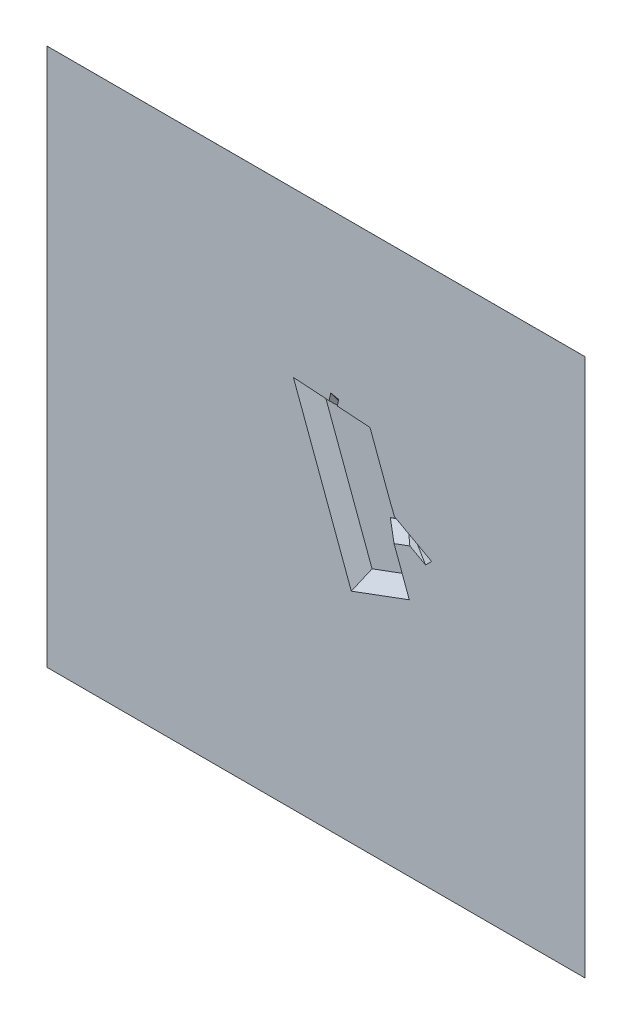
SolidWorks part; units mm, degrees
ref_plane "Front Plane" through (0, 0, 0) normal (0, 0, 1) x (1, 0, 0)
ref_plane "Top Plane" through (0, 0, 0) normal (0, 1, 0) x (1, 0, 0)
ref_plane "Right Plane" through (0, 0, 0) normal (1, 0, 0) x (0, 0, -1)
sketch "Sketch3" plane through (0, 0, 0) normal (0, 0, 1) x (1, 0, 0)
  line L1 (250000, 250000) -> (-250000, 250000)
  line L2 (250000, 250000) -> (250000, -250000)
  line L3 (250000, -250000) -> (-250000, -250000)
  line L4 (-250000, 250000) -> (-250000, -250000)
  line L5 (250000, 250000) -> (-250000, -250000) construction
  line L6 (250000, -250000) -> (-250000, 250000) construction
  point P0 (0, 0)
  dimension "D1" = 500000
  dimension "D2" = 500000
extrude "Boss-Extrude1" add sketch "Sketch3" against normal blind 15000
sketch "Sketch2" plane through (0, 0, 0) normal (0, 0, 1) x (1, 0, 0)
  line L0 (-17377.0412, 88071.2876) -> (32833.2448, -47278.1791)
  line L1 (-17377.0412, 88071.2876) -> (10112.1552, 86264.6887)
  line L2 (10112.1552, 86264.6887) -> (13737.5816, 102715.7946)
  line L3 (13737.5816, 102715.7946) -> (21089.3357, 101095.6455)
  line L4 (21089.3357, 101095.6455) -> (17710.8971, 85765.2969)
  line L5 (68877.8782, 42815.8741) -> (72921.953, 32726.7803)
  line L6 (45501.4717, 34143.9813) -> (68877.8782, 42815.8741) construction
  line L7 (68877.8782, 42815.8741) -> (53825.5063, 83391.8331)
  line L8 (17710.8971, 85765.2969) -> (53825.5063, 83391.8331)
  line L9 (18073.9152, 35635.2282) -> (6825.7271, 65956.4311) construction
  line L10 (32833.2448, -47278.1791) -> (75451.4702, -31468.1923)
  line L11 (75451.4702, -31468.1923) -> (57125.4375, 17932.4176)
  line L12 (57125.4375, 17932.4176) -> (73215.3416, 23901.253)
  line L13 (73215.3416, 23901.253) -> (101844.2457, 8294.7719)
  line L14 (101844.2457, 8294.7719) -> (107465.1822, 13896.2218)
  line L15 (107465.1822, 13896.2218) -> (82661.4814, 27417.4689)
  line L16 (82661.4814, 27417.4689) -> (72921.953, 32726.7803)
  line L17 (66452.5436, 88076.0566) -> (6825.7271, 65956.4311) construction
  line L18 (25140.4514, 16586.3048) -> (19465.1425, 31884.9633) construction
  dimension "D1" = 15000
extrude "Cut-Extrude3" cut sketch "Sketch2" against normal blind 12180
sketch "Sketch4" plane through (19388.8566, -52265.6135, 0) normal (-0.3478, 0.9376, 0) x (0.9376, 0.3478, 0)
  line L0 (14339.6679, 0) -> (26339.6679, 12180)
  line L1 (14339.6679, 12180) -> (59795.8976, 12180) construction
  line L2 (26339.6679, 12180) -> (14339.6679, 12180)
  line L3 (14339.6679, 12180) -> (14339.6679, 0)
  dimension "D1" = 12000
extrude "Boss-Extrude2" add sketch "Sketch4" along normal up to next
sketch "Sketch5" plane through (56062.6136, 20797.4212, 0) normal (-0.9376, -0.3478, 0) x (0, 0, 1)
  line L0 (0, -55746.0502) -> (-12180, -43746.0502)
  line L1 (-12180, -55746.0502) -> (-12180, -3055.788) construction
  line L2 (-12180, -43746.0502) -> (-12180, -55746.0502)
  line L3 (-12180, -55746.0502) -> (0, -55746.0502)
  dimension "D1" = 12000
extrude "Boss-Extrude3" add sketch "Sketch5" along normal up to next
sketch "Sketch6" plane through (26817.2698, 49194.2445, 0) normal (0.4786, 0.878, 0) x (0.878, -0.4786, 0)
  line L0 (85450.6523, 0) -> (85450.6523, 12180)
  line L1 (85450.6523, 12180) -> (52844.2664, 12180)
  line L2 (52844.2664, 12180) -> (85450.6523, 0)
extrude "Boss-Extrude4" add sketch "Sketch6" along direction (0.7083, 0.7059, 0) on the side of the normal up to next (7608.5222 mm away)
chamfer "Chamfer1" distance 12000 angle 45 1 edges at (66288.4539, -6767.8874, 0)
chamfer "Chamfer2" distance 12000 angle 45 1 edges at (70795.7869, 23003.6762, 0)
chamfer "Chamfer3" distance 9500 angle 45 2 edges at (-3632.443, 87167.9881, 0) (35768.2017, 84578.565, 0)
shell "Shell2" thickness 10 removed face at (0, -250000, -7500) removed face at (-250000, 0, -7500) removed face at (0, 250000, -7500) removed face at (250000, 0, -7500) removed face at (0, 0, -15000)
chamfer "Chamfer4" [suppressed] distance 10000 angle 45
sketch "Sketch9" plane through (-1134.6004, 250.0385, 0) normal (-0.9766, 0.2152, 0) x (0, 0, 1)
  line L0 (-12180, 103265.3852) -> (0, 103265.3852)
  line L1 (0, 103265.3852) -> (-12180, 87567.1867)
  line L2 (-12180, 87567.1867) -> (-12180, 103265.3852)
extrude "Boss-Extrude5" add sketch "Sketch9" along direction (-0.9766, 0.2152, 0) on the side of the normal up to next (7528.1586 mm away)
